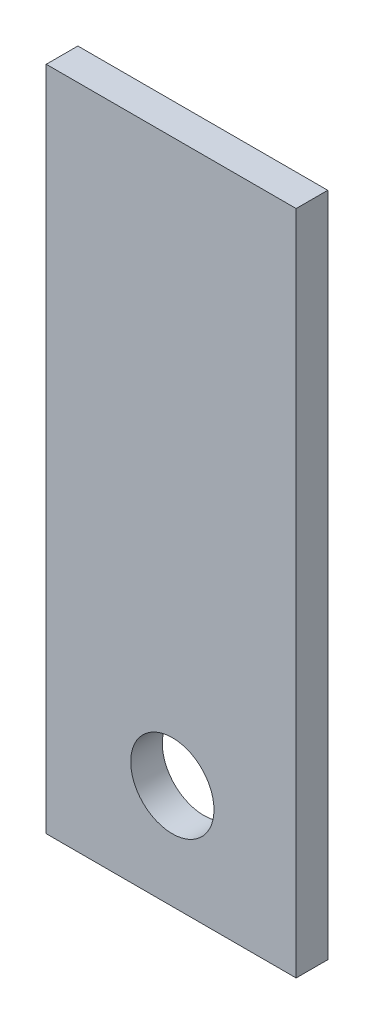
SolidWorks part; units mm, degrees
ref_plane "Front Plane" through (0, 0, 0) normal (0, 0, 1) x (1, 0, 0)
ref_plane "Top Plane" through (0, 0, 0) normal (0, 1, 0) x (1, 0, 0)
ref_plane "Right Plane" through (0, 0, 0) normal (1, 0, 0) x (0, 0, -1)
sketch "Sketch1" plane through (0, 0, 0) normal (0, 0, 1) x (1, 0, 0)
  line L1 (-19.0822, -4.3477) -> (-4.0822, -4.3477)
  line L2 (-19.0822, -4.3477) -> (-19.0822, 35.6523)
  line L3 (-19.0822, 35.6523) -> (-4.0822, 35.6523)
  line L4 (-4.0822, -4.3477) -> (-4.0822, 35.6523)
  dimension "D1" = 15
  dimension "D2" = 40
base flange "Base-Flange1" sketch "Sketch1" thickness 1.8974 reverse thickness direction no parameters "D1"=2.54
sketch "Sketch6" plane through (0, 0, 0) normal (0, 0, 1) x (1, 0, 0)
  circle A0 centre (-11.5134, 1.9319) radius 2.5
extrude "Cut-Extrude1" cut sketch "Sketch6" against normal blind 2 normal cut yes
sketch "Bend-Lines1" plane through (0, 0, 0) normal (0, 1, 0) x (1, 0, 0)
sketch "Bounding-Box1" plane through (0, 0, 0) normal (0, 1, 0) x (1, 0, 0)
sheet metal parameters "Sheet-Metal1" thickness 1.8974 parameters "D1"=2.54
flat pattern "Flat-Pattern1" [suppressed]
sketch "Bend-Lines2" plane through (0, 0, 0) normal (0, 1, 0) x (1, 0, 0)
sketch "Bounding-Box2" [suppressed] plane through (0, 0, 0) normal (0, 1, 0) x (1, 0, 0)
sheet metal parameters "Sheet-Metal2" thickness 1.8974 parameters "D1"=2.54
flat pattern "Flat-Pattern1"
sketch "Bend-Lines2" plane through (0, 0, 0) normal (0, 1, 0) x (1, 0, 0)
sketch "Bounding-Box2" [suppressed] plane through (0, 0, 0) normal (0, 1, 0) x (1, 0, 0)
